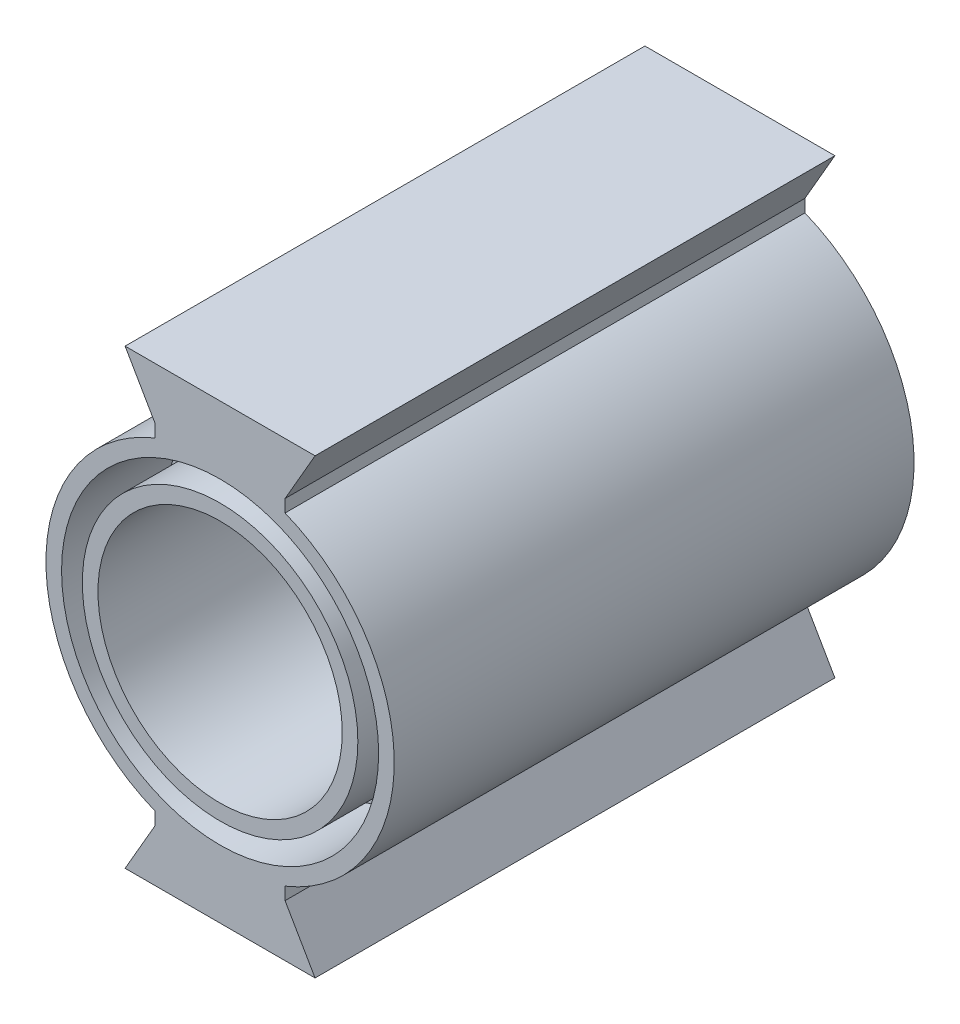
SolidWorks part; units mm, degrees
ref_plane "Front" through (0, 0, 0) normal (0, 0, 1) x (1, 0, 0)
ref_plane "Top" through (0, 0, 0) normal (0, 1, 0) x (1, 0, 0)
ref_plane "Right" through (0, 0, 0) normal (1, 0, 0) x (0, 0, -1)
sketch "Sketch1" plane through (0, 0, 0) normal (0, 0, 1) x (1, 0, 0)
  circle A0 centre (0, 0) radius 5.969
  circle A1 centre (0, 0) radius 8.509
  dimension "D1" = 11.938
  dimension "D2" = 17.018
extrude "Boss-Extrude1" add sketch "Sketch1" along normal blind 25.4
sketch "Sketch2" plane through (0, 0, 25.4) normal (0, 0, 1) x (1, 0, 0)
  circle A0 centre (0, 0) radius 6.731
  circle A1 centre (0, 0) radius 7.747
  dimension "D1" = 13.462
  dimension "D2" = 15.494
extrude "Cut-Extrude1" cut sketch "Sketch2" against normal blind 5.08
sketch "Sketch3" plane through (0, 0, 0) normal (0, 0, 1) x (1, 0, 0)
  line L4 (-3.175, 7.8945) -> (-3.175, 8.509)
  line L5 (3.175, 7.8945) -> (3.175, 8.509)
  line L6 (3.175, 8.509) -> (4.6415, 11.049)
  line L7 (4.6415, 11.049) -> (-4.6415, 11.049)
  line L8 (-4.6415, 11.049) -> (-3.175, 8.509)
  line L9 (-3.175, 8.509) -> (3.175, 8.509) construction
  circle A2 centre (0, 0) radius 8.509 construction
  arc A3 (-3.175, 7.8945) -> (3.175, 7.8945) centre (0, 0) cw
  point P10 (0, 8.509)
  dimension "D1" = 17.018
  dimension "D2" = 6.35
  dimension "D3" = 60
  dimension "D4" = 60
  dimension "D5" = 2.54
extrude "Boss-Extrude2" add sketch "Sketch3" along normal up to surface (25.4 mm away) up to face at (7.747, 0, 25.4)
mirror "Mirror1" about plane through (0, 0, 0) normal (0, 1, 0) of "Boss-Extrude2"
